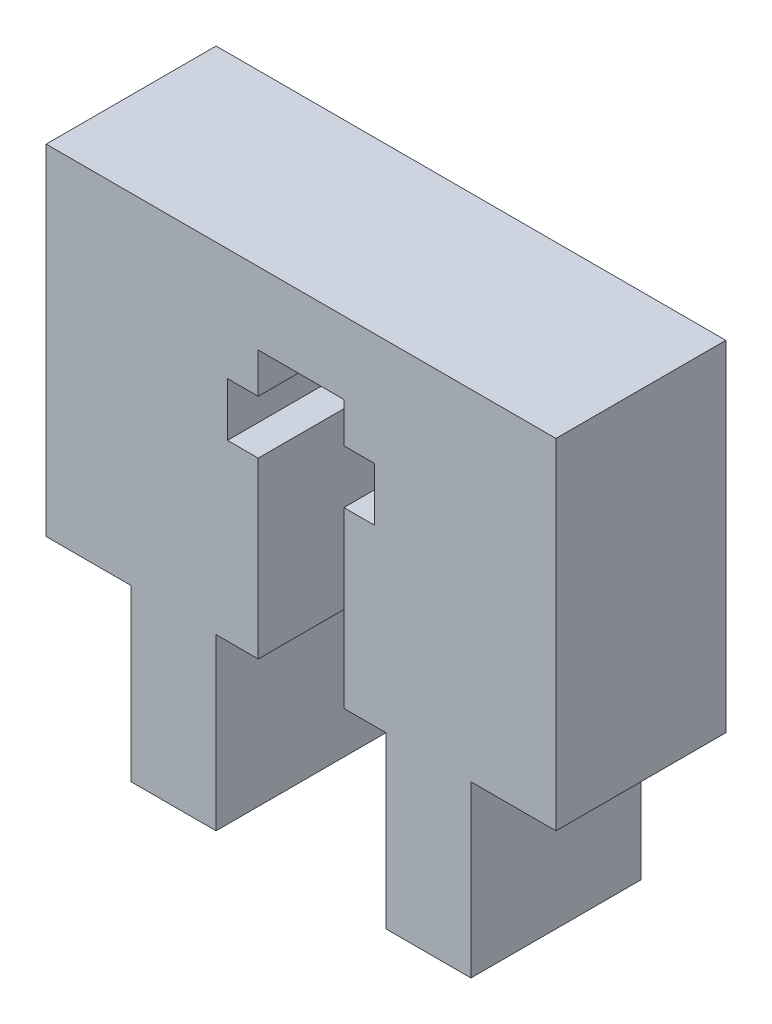
SolidWorks part; units mm, degrees
ref_plane "Front Plane" through (0, 0, 0) normal (0, 0, 1) x (1, 0, 0)
ref_plane "Top Plane" through (0, 0, 0) normal (0, 1, 0) x (1, 0, 0)
ref_plane "Right Plane" through (0, 0, 0) normal (1, 0, 0) x (0, 0, -1)
sketch "Sketch1" plane through (0, 0, 0) normal (0, 0, 1) x (1, 0, 0)
  line L0 (-3.175, 12.7) -> (15.875, 12.7)
  line L1 (3.175, 0) -> (9.525, 0)
  line L14 (0, 0) -> (0, -6.35)
  line L15 (0, -6.35) -> (3.175, -6.35)
  line L16 (3.175, 0) -> (3.175, -6.35)
  line L18 (12.7, 0) -> (12.7, -6.35)
  line L19 (12.7, -6.35) -> (9.525, -6.35)
  line L20 (9.525, 0) -> (9.525, -6.35)
  line L23 (0, 0) -> (-3.175, 0)
  line L24 (-3.175, 12.7) -> (-3.175, 0)
  line L27 (12.7, 0) -> (15.875, 0)
  line L28 (15.875, 12.7) -> (15.875, 0)
  dimension "D1" = 12.7
  dimension "D3" = 6.35
  dimension "D5" = 19.05
extrude "Boss-Extrude1" add sketch "Sketch1" along normal blind 6.35
sketch "Sketch3" plane through (0, 0, 6.35) normal (0, 0, 1) x (1, 0, 0)
  line L0 (3.175, 0) -> (9.525, 0) construction
  line L1 (4.75, 0) -> (7.95, 0)
  line L2 (4.75, 0) -> (4.75, 6.5)
  line L3 (4.75, 10) -> (7.95, 10)
  line L4 (7.95, 0) -> (7.95, 6.5)
  line L5 (6.35, 0) -> (6.35, 10) construction
  line L6 (4.75, 8.5) -> (3.6, 8.5)
  line L7 (7.95, 8.5) -> (7.95, 10)
  line L8 (4.75, 6.5) -> (3.6, 6.5)
  line L9 (3.6, 8.5) -> (3.6, 6.5)
  line L10 (7.95, 8.5) -> (9.1, 8.5)
  line L12 (7.95, 6.5) -> (9.1, 6.5)
  line L13 (9.1, 8.5) -> (9.1, 6.5)
  line L14 (3.6, 7.5) -> (9.1, 7.5) construction
  line L15 (4.75, 8.5) -> (4.75, 10)
  point P18 (6.35, 0)
  dimension "D1" = 10
  dimension "D2" = 7.5
  dimension "D3" = 2
  dimension "D4" = 5.5
  dimension "D5" = 3.2
extrude "Cut-Extrude3" cut sketch "Sketch3" against normal through all
